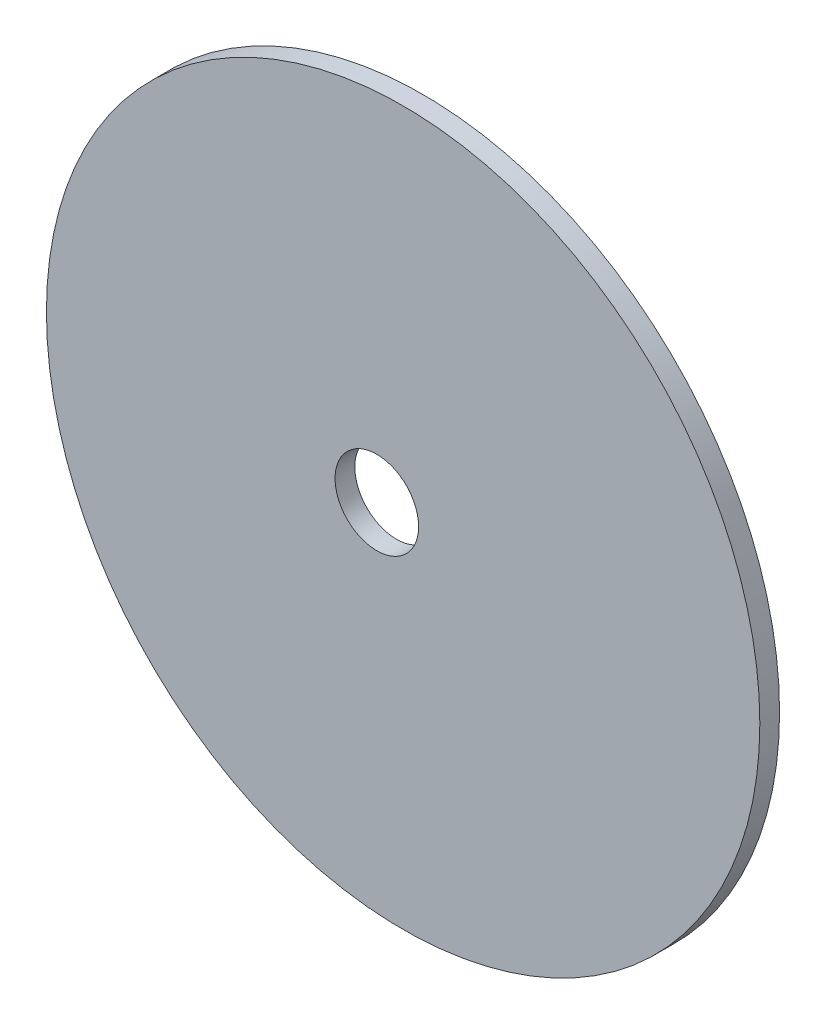
SolidWorks part; units mm, degrees
ref_plane "Front Plane" through (0, 0, 0) normal (0, 0, 1) x (1, 0, 0)
ref_plane "Top Plane" through (0, 0, 0) normal (0, 1, 0) x (1, 0, 0)
ref_plane "Right Plane" through (0, 0, 0) normal (1, 0, 0) x (0, 0, -1)
sketch "Sketch1" plane through (0, 0, 0) normal (0, 0, 1) x (1, 0, 0)
  circle A0 centre (0, 0) radius 54.2271
  circle A2 centre (-4, 0) radius 6.35
  point P5 (0, 0)
  point P6 (0, 0)
  point P7 (0, 0)
extrude "Boss-Extrude5" add sketch "Sketch1" along normal blind 3 contours A2 | A0 region at (-4, 0, 0)
